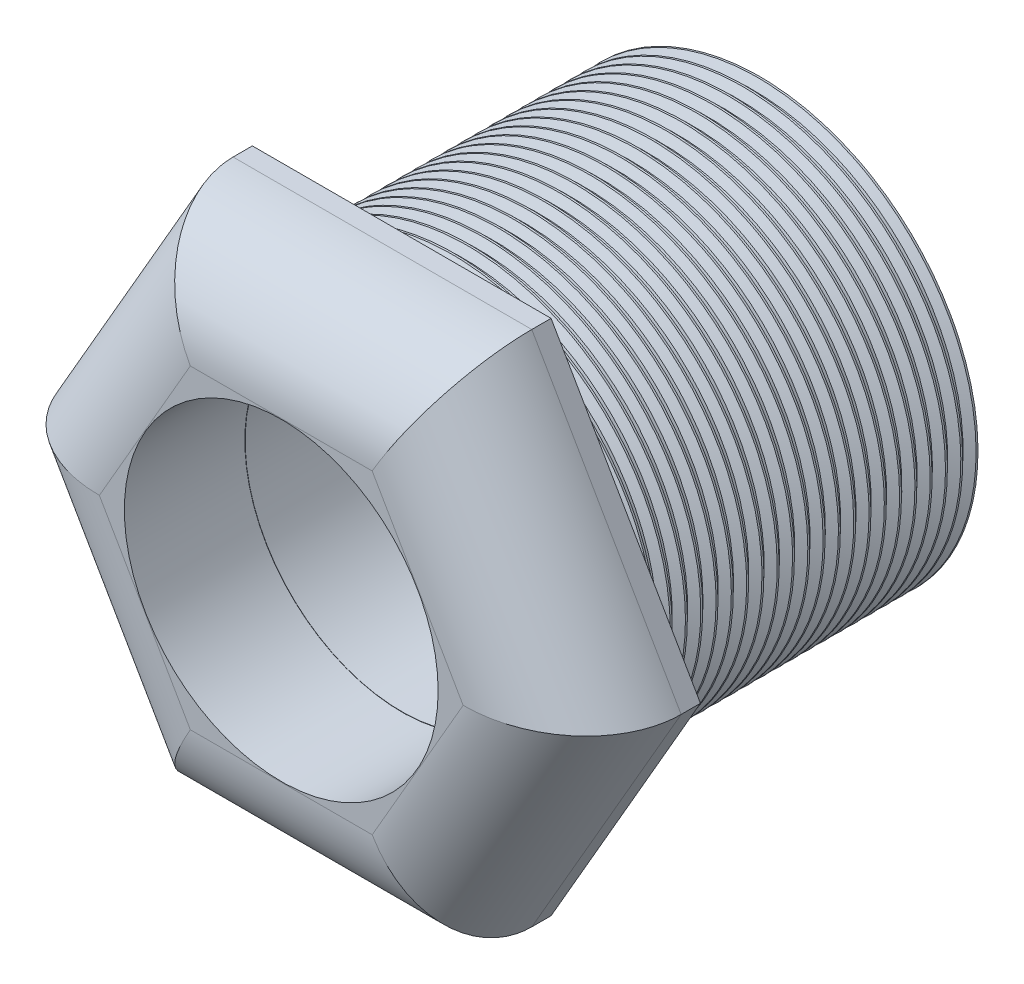
SolidWorks part; units mm, degrees
ref_plane "Front Plane" through (0, 0, 0) normal (0, 0, 1) x (1, 0, 0)
ref_plane "Top Plane" through (0, 0, 0) normal (0, 1, 0) x (1, 0, 0)
ref_plane "Right Plane" through (0, 0, 0) normal (1, 0, 0) x (0, 0, -1)
sketch "Sketch1" plane through (0, 0, 0) normal (0, 0, 1) x (1, 0, 0)
  circle A0 centre (0, 0) radius 3.25
  circle A1 centre (0, 0) radius 4.5
  dimension "D1" = 6.5
  dimension "D2" = 9
extrude "Boss-Extrude1" add sketch "Sketch1" along normal blind 7.5
thread "Thread1" pitch 0.3175 method cut profile "Thread Profile1" start angle 0, offset 0, length 7.5, pitch 0.3175, diameter 9
ref_plane "Plane1" through (-4.5, 0, 7.5) normal (0, -1, 0) x (-1, 0, 0)
sketch "Thread Profile1" plane through (-4.5, 0, 7.5) normal (0, -1, 0) x (-1, 0, 0)
  line L0 (0, 0) -> (0, 0.3175) construction
  line L11 (0, 0) -> (0, 0.2778)
  line L12 (0, 0.2778) -> (-0.1719, 0.1786)
  line L13 (-0.1719, 0.1786) -> (-0.1719, 0.0992)
  line L15 (-0.1719, 0.0992) -> (0, 0)
  line L17 (-0.1719, 0.1389) -> (0, 0.1389) construction
  point P2 (0, 0)
  dimension "Pitch" = 0.3175
  dimension "Profile_Angle" = 60
  dimension "Profile_Land" = 0.0794
  dimension "Profile_Height" = 0.1719
sketch "Sketch4" plane through (0, 0, 7.5) normal (0, 0, 1) x (1, 0, 0)
  circle A0 centre (0, 0) radius 3.2566
  circle A1 centre (0, 0) radius 6.2
  dimension "D1" = 12.4
extrude "Boss-Extrude2" add sketch "Sketch4" along normal blind 2.5
sketch "Sketch5" plane through (0, 0, 10) normal (0, 0, 1) x (1, 0, 0)
  line L0 (-3.1, 5.3694) -> (3.1, 5.3694)
  line L1 (3.1, 5.3694) -> (6.2, 0)
  line L2 (6.2, 0) -> (3.1, -5.3694)
  line L3 (3.1, -5.3694) -> (-3.1, -5.3694)
  line L4 (-3.1, -5.3694) -> (-6.2, 0)
  line L5 (-6.2, 0) -> (-3.1, 5.3694)
  circle A0 centre (0, 0) radius 6.2 construction
  circle A1 centre (0, 0) radius 6.2
  circle M8 centre (0, 0) radius 6.2
  dimension "D1" = 6.2
  dimension "D2" = 6.2
  dimension "D3" = 6.2
extrude "Cut-Extrude2" cut sketch "Sketch5" against normal blind 2.5 contours L1 M8 | L2 M8 | L3 M8 | L4 M8 | L5 M8 | L0 M8 region at (0, 5.7036, 10) region at (-4.9395, 2.8518, 10) region at (4.9395, 2.8518, 10) region at (-4.9395, -2.8518, 10) region at (4.9395, -2.8518, 10) region at (0, -5.7036, 10)
fillet "Fillet4" radius 2.1 6 edges at (4.65, -2.6847, 10) (0, -5.3694, 10) (-4.65, -2.6847, 10) (-4.65, 2.6847, 10) (0, 5.3694, 10) (4.65, 2.6847, 10)
